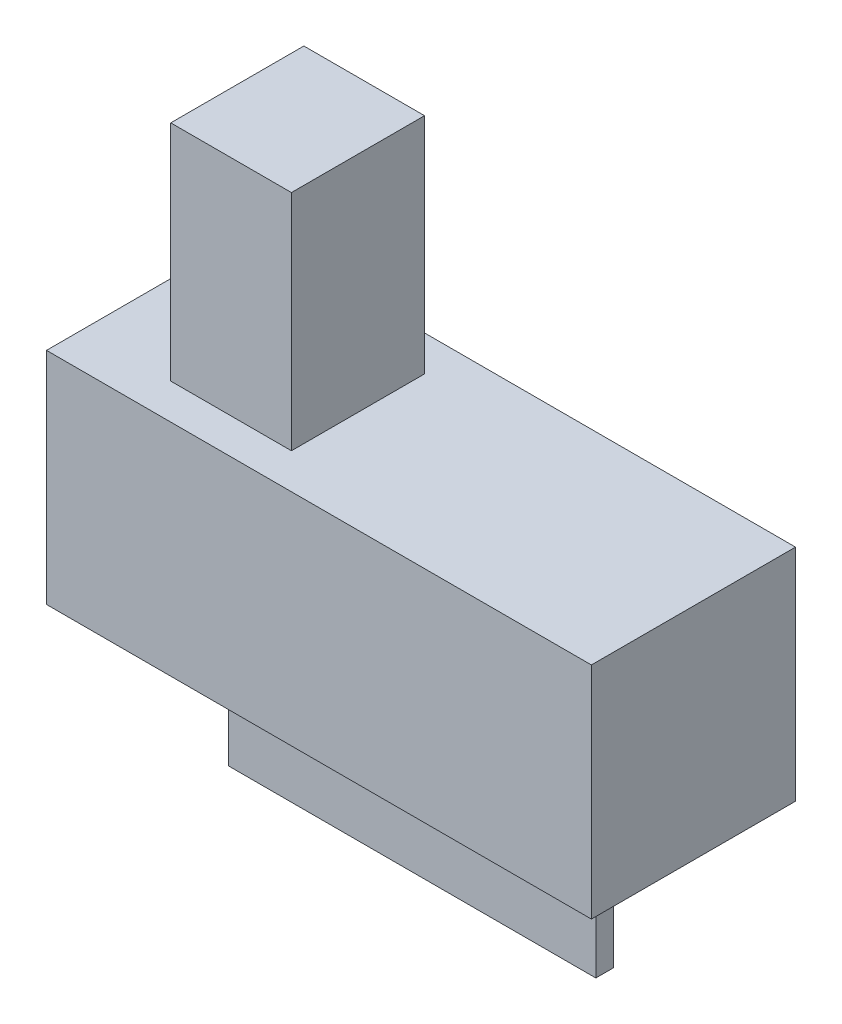
SolidWorks part; units mm, degrees
ref_plane "Plano frontal" through (0, 0, 0) normal (0, 0, 1) x (1, 0, 0)
ref_plane "Plano superior" through (0, 0, 0) normal (0, 1, 0) x (1, 0, 0)
ref_plane "Plano direito" through (0, 0, 0) normal (1, 0, 0) x (0, 0, -1)
sketch "Esboço2" plane through (0, 0, 0) normal (0, 1, 0) x (1, 0, 0)
  line L1 (0, 0) -> (15.35, 0)
  line L2 (0, 0) -> (0, 5.75)
  line L3 (0, 5.75) -> (15.35, 5.75)
  line L4 (15.35, 0) -> (15.35, 5.75)
  line L5 (5.9, 4.75) -> (5.9, 1)
  line L8 (2.5, 4.75) -> (2.5, 1)
  line L9 (2.5, 1) -> (12.85, 1)
  line L10 (12.85, 1) -> (12.85, 4.75)
  line L11 (12.85, 4.75) -> (2.5, 4.75)
extrude "Ressalto-extrusão1" add sketch "Esboço2" against normal blind 6.2 contours L1 L4 L3 L2 L11 L10 L9 L8 | L5 L11 L8 L9 | L10 L11 L5 L9 region at (0.1639, 0, -2.875) region at (9.375, 0, -2.875) region at (4.2, 0, -2.875)
extrude "Ressalto-extrusão2" add sketch "Esboço2<3>" along normal blind 6.3 contours L5 L11 L8 L9 region at (4.2, 0, -2.875)
sketch "Esboço2<3>" plane through (0, 0, 0) normal (0, 1, 0) x (1, 0, 0) same geometry as "Esboço2"
sketch "Esboço3" plane through (0, -6.2, 0) normal (0, -1, 0) x (1, 0, 0)
  line L2 (2.5, -2.875) -> (2.5, -2.625)
  line L3 (2.5, -2.875) -> (2.5, -3.125)
  line L6 (12.85, -2.875) -> (12.85, -2.625)
  line L7 (12.85, -2.625) -> (2.5, -2.625)
  line L8 (12.85, -2.875) -> (12.85, -3.125)
  line L9 (12.85, -3.125) -> (2.5, -3.125)
extrude "Ressalto-extrusão3" add sketch "Esboço3" along normal blind 4
